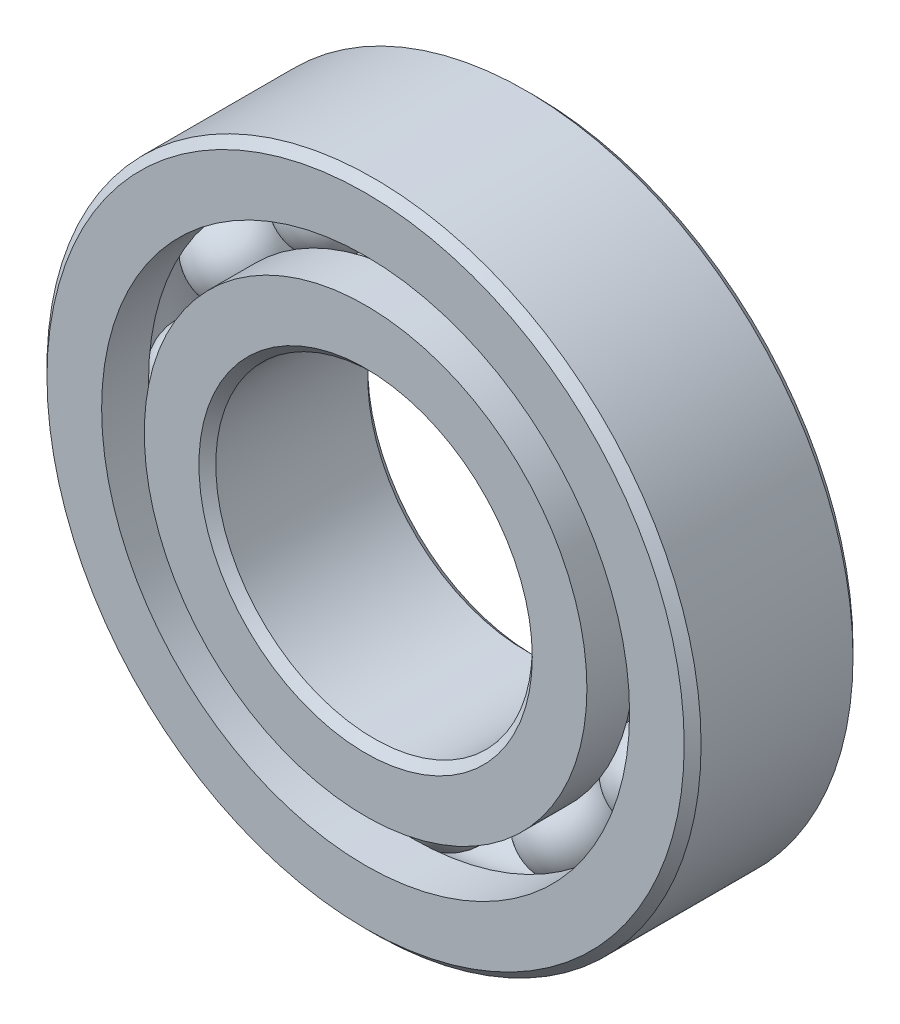
SolidWorks part; units mm, degrees
ref_plane "Front Plane" through (0, 0, 0) normal (0, 0, 1) x (1, 0, 0)
ref_plane "Top Plane" through (0, 0, 0) normal (0, 1, 0) x (1, 0, 0)
ref_plane "Right Plane" through (0, 0, 0) normal (1, 0, 0) x (0, 0, -1)
sketch "Sketch1" plane through (0, 0, 0) normal (1, 0, 0) x (0, 0, -1)
  line L0 (-8, 0) -> (8, 0) construction
  line L1 (0, 31) -> (0, -31) construction
  line L2 (7.2, 31) -> (-7.2, 31)
  line L3 (-7.2, 31) -> (-8, 30.2)
  line L4 (-8, 30.2) -> (-8, 25.022)
  line L5 (-8, 25.022) -> (-3.5556, 25.022)
  line L6 (8, 25.022) -> (3.5556, 25.022)
  line L7 (8, 30.2) -> (8, 25.022)
  line L8 (7.2, 31) -> (8, 30.2)
  line L9 (0, 31) -> (0, 23) construction
  line L10 (0, 23) -> (0, 15) construction
  arc A0 (-3.5556, 25.022) -> (3.5556, 25.022) centre (0, 23) cw
  point P14 (0, 15)
  dimension "Width" = 16
  dimension "OD" = 62
  dimension "D1" = 45
  dimension "D2" = 0.8
  dimension "Shaft Dia" = 30
  dimension "D3" = 7.1111
  dimension "D4" = 2.022
revolve "Revolve1" add sketch "Sketch1" angle 360 about L0
sketch "Sketch3" plane through (0, 0, 0) normal (1, 0, 0) x (0, 0, -1)
  line L0 (-8, 20.978) -> (-3.5556, 20.978)
  line L1 (0, 31) -> (0, -31) construction
  line L2 (-8, 30.2) -> (-8, 25.022) construction
  line L3 (-8, 20.978) -> (-8, 15.8)
  line L4 (-7.2, 31) -> (-8, 30.2) construction
  line L5 (-8, 15.8) -> (-7.2, 15)
  line L6 (-7.2, 15) -> (7.2, 15)
  line L7 (7.2, 31) -> (7.2, -31) construction
  line L8 (7.2, 15) -> (8, 15.8)
  line L9 (8, -30.2) -> (8, 30.2) construction
  line L10 (8, 15.8) -> (8, 20.978)
  line L11 (8, 20.978) -> (3.5556, 20.978)
  line L13 (7.2, 31) -> (8, 30.2) construction
  arc A0 (3.5556, 25.022) -> (-3.5556, 25.022) centre (0, 23) ccw construction
  arc A1 (3.5556, 20.978) -> (-3.5556, 20.978) centre (0, 23) cw
revolve "Revolve3" add sketch "Sketch3" angle 360 about L0
sketch "Sketch4" plane through (0, 0, 0) normal (1, 0, 0) x (0, 0, -1)
  line L0 (-4.0903, 23) -> (4.0903, 23)
  arc A2 (-4.0903, 23) -> (4.0903, 23) centre (0, 23) cw
  arc A3 (3.5556, 25.022) -> (-3.5556, 25.022) centre (0, 23) ccw construction
revolve "Revolve4" add sketch "Sketch4" angle 360 about L0
ref_axis "Axis1" through (0, 0, -8) along (0, 0, 1)
pattern_circular "CirPattern1" count 12 every 30 about axis through (0, 0, -8) along (0, 0, 1) of bodies 104
sketch "Sketch5" plane through (0, 0, 0) normal (1, 0, 0) x (0, 0, -1)
  line L0 (-8, 25.022) -> (-3.5556, 25.022) construction
  line L1 (-7.6, 25.022) -> (-4.0903, 25.022)
  line L2 (-7.6, 25.022) -> (-7.6, 20.978)
  line L3 (-7.6, 20.978) -> (-4.0903, 20.978)
  line L4 (-4.0903, 25.022) -> (-4.0903, 20.978)
  line L5 (-8, 20.978) -> (-3.5556, 20.978) construction
  line L6 (8, 25.022) -> (3.5556, 25.022) construction
  line L7 (7.6, 25.022) -> (4.0903, 25.022)
  line L8 (7.6, 25.022) -> (7.6, 20.978)
  line L9 (7.6, 20.978) -> (4.0903, 20.978)
  line L10 (4.0903, 25.022) -> (4.0903, 20.978)
  line L11 (8, 20.978) -> (3.5556, 20.978) construction
  line L12 (-7.2, 31) -> (-8, 30.2) construction
  point P18 (-7.6, 30.6)
equation "\"D2@Sketch1\" = \"Width@Sketch1\"*.05"
equation "\"D3@Sketch1\" = \"Width@Sketch1\"/2.25"
equation "\"D4@Sketch1\" = (((\"OD@Sketch1\"-\"Width@Sketch1\")/2)/3.25)/3.5"
equation "\"D2@CirPattern1\" = 360/\"Balls@CirPattern1\""
